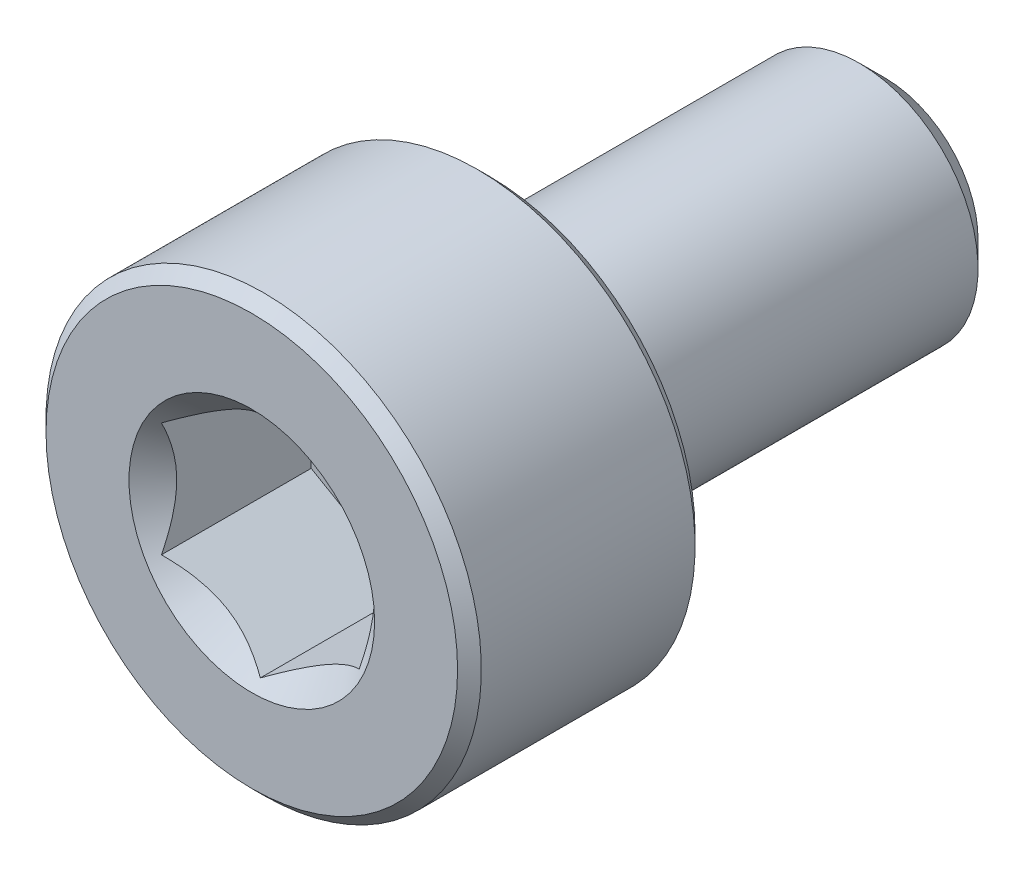
SolidWorks part; units mm, degrees
material "Alloy Steel"
ref_plane "Front Plane" through (0, 0, 0) normal (0, 0, 1) x (1, 0, 0)
ref_plane "Top Plane" through (0, 0, 0) normal (0, 1, 0) x (1, 0, 0)
ref_plane "Right Plane" through (0, 0, 0) normal (1, 0, 0) x (0, 0, -1)
sketch "Sketch1" plane through (0, 0, 0) normal (1, 0, 0) x (0, 0, -1)
  line L0 (-4, 0) -> (4, 0) construction
  line L1 (4, 0) -> (4, 1.1752) construction
  line L2 (4, 1.1752) -> (3.6752, 1.5) construction
  line L3 (3.6752, 1.5) -> (3.625, 1.5) construction
  line L4 (3.625, 1.5) -> (-1, 1.5) construction
  line L5 (-1, 1.5) -> (-1, 2.75) construction
  line L6 (-1, 2.75) -> (-4, 2.75) construction
  line L7 (-4, 2.75) -> (-4, 0) construction
  line L8 (4, 1.1752) -> (4, 1.5) construction
  line L9 (3.9688, 1.5541) -> (4.2188, 1.1211) construction
  line L10 (4.2188, 1.1211) -> (4.4688, 1.5541) construction
  line L11 (4.4688, 1.5541) -> (3.9688, 1.5541) construction
  line L12 (4.2188, 1.5541) -> (4.2188, 1.5) construction
  line L13 (4.2188, 1.1211) -> (4.2188, 1.1752) construction
  line L14 (4.1875, 1.1752) -> (4.25, 1.1752) construction
  line L15 (4, 1.5) -> (4.4375, 1.5) construction
  line L16 (3.9844, 1.5271) -> (4.4531, 1.5271) construction
  line L17 (4, 0) -> (4, -1.5) construction
  line L18 (-1.15, 2.75) -> (-1, 2.6) construction
  line L19 (-3.85, 2.75) -> (-4, 2.6) construction
  line L20 (-1, 1.5) -> (-1, 0) construction
  line L21 (-1, 0.75) -> (0.6667, 0.75) construction
  line L22 (0.6667, 0.75) -> (2.3333, 0.75) construction
  line L23 (2.3333, 0.75) -> (4, 0.75) construction
  line L24 (0.6667, 0.75) -> (0.6667, 1.5) construction
  line L25 (0.6667, 1.5) -> (0.6667, 2.75) construction
  line L26 (2.3333, 0.75) -> (2.3333, 2.75) construction
  point P0 (-4, 1.25)
  point P3 (2.75, 1.5)
  point P4 (0, 0)
  point P18 (2.3333, 1.5)
  point P22 (4.2188, 1.1752)
  point P24 (3.625, 1.5)
  point P25 (4.2188, 1.5)
  point P28 (4.2188, 1.5271)
  point P29 (2.75, -1.5)
  point P30 (0.6667, 1.5)
  point P31 (-2.5, 2.75)
  point P37 (-1.525, 2.75)
  point P38 (-3.775, 2.75)
  point P45 (0.6667, 0.75)
  point P46 (2.3333, 0.75)
  dimension "D2" = 0.0625
  dimension "D7" = 0.15
  dimension "D8" = 0.15
  dimension "D9" = 0.15
  dimension "D10" = 0.075
  dimension "D11" = 0.375
  dimension "Drive Size" = 2.5
  dimension "Head Diameter" = 5.5
  dimension "Head Height" = 3
  dimension "Thread Pitch" = 0.5
  dimension "Thread Dia" = 3
  dimension "Length" = 5
  dimension "D12" = 0.375
  dimension "D4" = 1.25
  dimension "D3" = 45
sketch "Sketch2" plane through (0, 0, 0) normal (1, 0, 0) x (0, 0, -1)
  line L0 (-4, 0) -> (-4, 2.6)
  line L1 (-3.85, 2.75) -> (-1.15, 2.75)
  line L2 (-1, 2.6) -> (-1, 1.65)
  line L4 (3.6752, 1.5) -> (4, 1.1752)
  line L5 (4, 1.1752) -> (4, 0)
  line L6 (-1, 2.75) -> (-4, 2.75) construction
  line L7 (4, 0) -> (-4, 0)
  line L8 (-3.85, 2.75) -> (-4, 2.6) construction
  line L10 (-3.85, 2.75) -> (-4, 2.6)
  line L14 (-1.15, 2.75) -> (-1, 2.6) construction
  line L16 (-1.15, 2.75) -> (-1, 2.6)
  line L17 (-1, 1.5) -> (-1, 2.75) construction
  line L19 (-0.85, 1.5) -> (3.6752, 1.5)
  line L20 (3.625, 1.5) -> (-1, 1.5) construction
  arc A1 (-1, 1.65) -> (-0.85, 1.5) centre (-0.85, 1.65) ccw
  dimension "D3" = 0.15
revolve "Revolve1" add sketch "Sketch2" angle 360 about L7
sketch "Sketch3" plane through (0, 0, 4) normal (0, 0, 1) x (1, 0, 0)
  line L1 (1.25, -0.7217) -> (1.25, 0.7217)
  line L2 (1.25, 0.7217) -> (0, 1.4434)
  line L3 (0, 1.4434) -> (-1.25, 0.7217)
  line L4 (-1.25, 0.7217) -> (-1.25, -0.7217)
  line L5 (-1.25, -0.7217) -> (0, -1.4434)
  line L6 (0, -1.4434) -> (1.25, -0.7217)
  circle A0 centre (0, 0) radius 1.25 construction
  circle A1 centre (0, 0) radius 2.75 construction
  circle A2 centre (0, 0) radius 2.75 construction
  circle A3 centre (0, 0) radius 1.4434 construction
  point P13 (0, 0)
  dimension "D1" = 2.8868
extrude "Cut-Extrude1" cut sketch "Sketch3" against normal offset from surface (2 mm away) 1 up to face at (0, 2.6, 1)
sketch "Sketch4" plane through (0, 0, 4) normal (0, 0, 1) x (1, 0, 0)
  circle A0 centre (0, 0) radius 1.5516
  dimension "D1" = 3.1033
extrude "Cut-Extrude2" cut sketch "Sketch4" against normal up to vertex (1.5 mm away) draft 45 up to point (0, 2.75, 2.5)
sketch "Sketch11" plane through (0, 0, 0) normal (1, 0, 0) x (0, 0, -1)
  line L0 (-4, 0) -> (4, 0) construction
  line L1 (-4, 0) -> (4, 0) construction
  line L2 (-0.0625, 0) -> (-0.0625, 1.5) construction
  line L3 (3.625, 1.5) -> (-1, 1.5) construction
  line L4 (3.0625, 0) -> (3.0625, 1.5) construction
  line L6 (4, 1.1752) -> (4, 1.5) construction
  point P2 (-0.0625, 0)
  point P3 (3.0625, 0)
  dimension "D1" = 0.9375
  dimension "D2" = 0.9375
sketch "Sketch6" [suppressed] plane through (0, 0, -4) normal (0, 0, -1) x (-1, 0, 0)
  circle A0 centre (0, 0) radius 1.5
curve "Helix/Spiral1" [suppressed] pitch 0.5 height 5.5 turns 11
sketch "Sketch10" [suppressed] plane through (0, 0, 0) normal (1, 0, 0) x (0, 0, -1)
  line L0 (-0.85, -2.75) -> (-0.85, 2.75)
  line L5 (-4, 0) -> (4, 0) construction
  line L6 (-0.85, 1.5) -> (-0.85, -1.5) construction
  point P3 (-0.85, 0)
split "Split1" [suppressed] bodies to split 106
sketch "Sketch7" [suppressed] plane through (0, 0, 0) normal (1, 0, 0) x (0, 0, -1)
  line L0 (3.9844, 1.5271) -> (4.4531, 1.5271)
  line L1 (4.4531, 1.5271) -> (4.25, 1.1752)
  line L2 (4.25, 1.1752) -> (4.1875, 1.1752)
  line L3 (4.1875, 1.1752) -> (3.9844, 1.5271)
sweep "Cut-Sweep1" [suppressed] cut profiles "Sketch7" path "Helix/Spiral1"
sketch "Sketch8" [suppressed] plane through (0, 0, 0) normal (1, 0, 0) x (0, 0, -1)
  line L0 (-1, 0) -> (-1, 1.5)
  line L1 (-0.85, -1.5) -> (-0.85, 1.5) construction
  line L2 (-1, 1.5) -> (-0.85, 1.5)
  line L4 (-0.85, 1.5) -> (0.016, 0)
  line L5 (0.016, 0) -> (-1, 0)
  line L6 (3.625, 1.5) -> (-1, 1.5) construction
  line L7 (-4, 0) -> (4, 0) construction
  dimension "D1" = 60
revolve "Revolve2" [suppressed] add sketch "Sketch8" angle 360 about L5
equation "\"D2@Sketch1\" = \"Thread Pitch@Sketch1\" / 8"
equation "\"D4@Helix/Spiral1\" = \"Thread Pitch@Sketch1\""
equation "\"D7@Sketch1\" = \"Head Height@Sketch1\" * .05"
equation "\"D8@Sketch1\"=\"D7@Sketch1\""
equation "\"D9@Sketch1\"=\"D7@Sketch1\""
equation "\"D10@Sketch1\"=\"D7@Sketch1\"/2"
equation "\"D11@Sketch1\"=\"D10@Sketch1\"*5"
equation "\"D4@Sketch1\"=\"Thread Pitch@Sketch1\"*2.5"
equation "\"D12@Sketch1\"=\"Thread Pitch@Sketch1\"*.75"
equation "\"D3@Helix/Spiral1\"=\"Length@Sketch1\"+\"Thread Pitch@Sketch1\""
equation "\"D3@Sketch2\"=\"Thread Dia@Sketch1\"*0.05"
equation "\"D1@Sketch11\"=\"Length@Sketch1\"*0.1875"
equation "\"D2@Sketch11\"=\"D1@Sketch11\""
equation "\"D1@Sketch4\"=\"D1@Sketch3\"*1.075"
